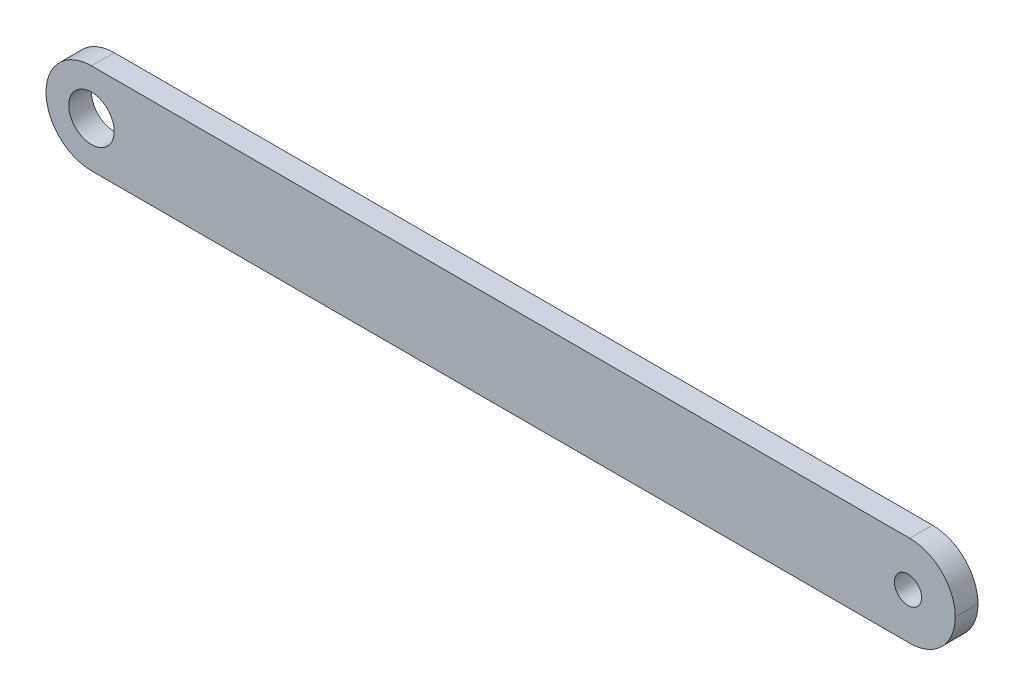
SolidWorks part; units mm, degrees
ref_plane "Front Plane" through (0, 0, 0) normal (0, 0, 1) x (1, 0, 0)
ref_plane "Top Plane" through (0, 0, 0) normal (0, 1, 0) x (1, 0, 0)
ref_plane "Right Plane" through (0, 0, 0) normal (1, 0, 0) x (0, 0, -1)
sketch "Sketch1" plane through (0, 0, 0) normal (0, 0, 1) x (1, 0, 0)
  line L1 (0, 0) -> (127, 0)
  line L2 (0, 0) -> (0, 12.7)
  line L3 (0, 12.7) -> (127, 12.7)
  line L4 (127, 0) -> (127, 12.7)
  dimension "D1" = 12.7
  dimension "D2" = 127
extrude "Boss-Extrude1" add sketch "Sketch1" along normal blind 3.175
fillet "Fillet1" radius 6.35 2 edges at (0, 0, 1.5875) (0, 12.7, 1.5875)
sketch "Sketch2" plane through (0, 0, 3.175) normal (0, 0, 1) x (1, 0, 0)
  line L1 (127, 0) -> (127, 12.7) construction
  line L2 (6.35, 0) -> (127, 0) construction
  line L3 (6.35, 0) -> (127, 0) construction
  circle A0 centre (6.35, 6.35) radius 3.175
  circle A1 centre (120.396, 6.35) radius 1.905
  dimension "D1" = 6.35
  dimension "D2" = 3.81
  dimension "D3" = 6.35
  dimension "D4" = 6.604
  dimension "D5" = 6.35
  dimension "D6" = 6.35
extrude "Cut-Extrude1" cut sketch "Sketch2" against normal blind 3.175
fillet "Fillet2" radius 6.35 2 edges at (127, 0, 1.5875) (127, 12.7, 1.5875)
